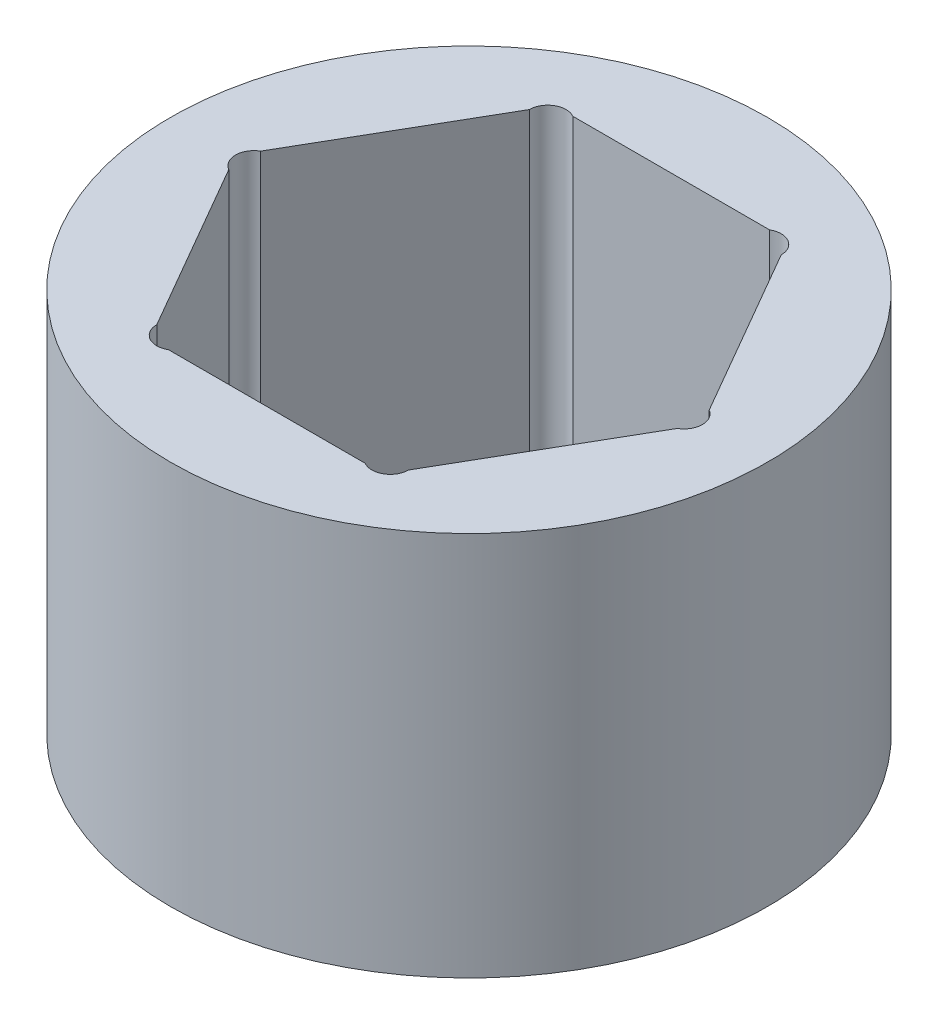
SolidWorks part; units mm, degrees
ref_plane "Front Plane" through (0, 0, 0) normal (0, 0, 1) x (1, 0, 0)
ref_plane "Top Plane" through (0, 0, 0) normal (0, 1, 0) x (1, 0, 0)
ref_plane "Right Plane" through (0, 0, 0) normal (1, 0, 0) x (0, 0, -1)
sketch "Sketch1" plane through (0, 0, 0) normal (0, 1, 0) x (1, 0, 0)
  line L0 (0, 0) -> (3.8128, 6.604) construction
  line L1 (7.6256, 0) -> (3.8128, 6.604)
  line L2 (3.8128, 6.604) -> (-3.8128, 6.604)
  line L3 (-3.8128, 6.604) -> (-7.6256, 0)
  line L4 (-7.6256, 0) -> (-3.8128, -6.604)
  line L5 (-3.8128, -6.604) -> (3.8128, -6.604)
  line L6 (3.8128, -6.604) -> (7.6256, 0)
  circle A0 centre (0, 0) radius 6.604 construction
  circle A1 centre (0, 0) radius 9.7536
  circle A2 centre (3.5128, 6.0844) radius 0.6
  circle A3 centre (7.0256, 0) radius 0.6
  circle A4 centre (3.5128, -6.0844) radius 0.6
  circle A5 centre (-3.5128, -6.0844) radius 0.6
  circle A6 centre (-7.0256, 0) radius 0.6
  circle A7 centre (-3.5128, 6.0844) radius 0.6
  point P25 (0, 0)
  dimension "D1" = 13.208
  dimension "D2" = 19.5072
  dimension "D3" = 1.2
  dimension "D4" = 6
extrude "Boss-Extrude1" add sketch "Sketch1" along normal blind 12.573 contours A1 A7 L2 A2 L1 A3 L6 A4 L5 A5 L4 A6 L3 region at (-9.4777, 0, 0)
